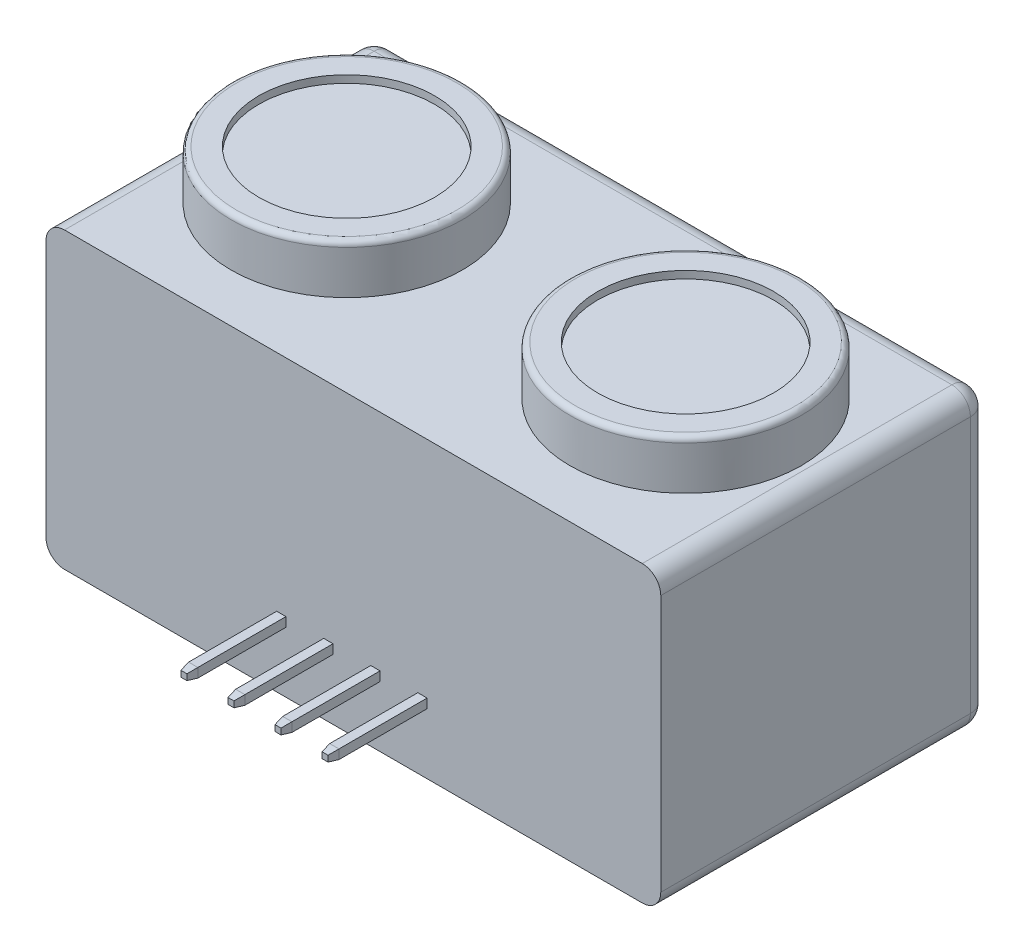
SolidWorks part; units mm, degrees
other "Camera1"
other "Camera3"
other "Camera4"
other "Camera5"
ref_plane "Front Plane" through (0, 0, 0) normal (0, 0, 1) x (1, 0, 0)
ref_plane "Top Plane" through (0, 0, 0) normal (0, 1, 0) x (1, 0, 0)
ref_plane "Right Plane" through (0, 0, 0) normal (1, 0, 0) x (0, 0, -1)
sketch "Sketch2" plane through (0, 0, 0) normal (0, 1, 0) x (1, 0, 0)
  line L1 (15.5, -8.5) -> (-15.5, -8.5)
  line L2 (15.5, -8.5) -> (15.5, 8.5)
  line L3 (15.5, 8.5) -> (-15.5, 8.5)
  line L4 (-15.5, -8.5) -> (-15.5, 8.5)
  line L5 (15.5, -8.5) -> (-15.5, 8.5) construction
  line L6 (15.5, 8.5) -> (-15.5, -8.5) construction
  point P0 (0, 0)
  dimension "D1" = 17
  dimension "D2" = 31
extrude "Boss-Extrude1" add sketch "Sketch2" along normal blind 1.5
sketch "Sketch3" plane through (0, 1.5, 0) normal (0, 1, 0) x (1, 0, 0)
  line L0 (0, 8.5) -> (0, -8.5) construction
  line L1 (15.5, 8.5) -> (-15.5, 8.5) construction
  line L2 (-15.5, -8.5) -> (15.5, -8.5) construction
  line L3 (-15.5, 8.5) -> (-15.5, -8.5) construction
  circle A0 centre (-9.15, 0) radius 6.25
  circle A1 centre (9.15, 0) radius 6.25
  point P10 (-15.4, 0)
  dimension "D1" = 12.5
  dimension "D2" = 0.1
extrude "Boss-Extrude2" add sketch "Sketch3" along normal blind 9
sketch "Sketch5" plane through (0, 0, 0) normal (0, -1, 0) x (1, 0, 0)
  line L0 (-15.5, 8.5) -> (15.5, 8.5) construction
  line L1 (-5.08, 5.86) -> (5.08, 5.86)
  line L2 (-5.08, 5.86) -> (-5.08, 8.4)
  line L3 (-5.08, 8.4) -> (5.08, 8.4)
  line L4 (5.08, 5.86) -> (5.08, 8.4)
  line L5 (-5.08, 7.13) -> (5.08, 7.13) construction
  line L6 (-2.54, 8.4) -> (-2.54, 5.86) construction
  line L7 (-3.56, 6.88) -> (-4.06, 6.88) construction
  line L8 (-3.56, 6.88) -> (-3.56, 7.38) construction
  line L9 (-3.56, 7.38) -> (-4.06, 7.38) construction
  line L10 (-4.06, 6.88) -> (-4.06, 7.38) construction
  line L11 (-3.56, 6.88) -> (-4.06, 7.38) construction
  line L12 (-3.56, 7.38) -> (-4.06, 6.88) construction
  line L13 (-4.06, 7.38) -> (-5.08, 7.38) construction
  line L14 (-4.06, 7.38) -> (-4.06, 8.4) construction
  line L15 (-3.56, 7.38) -> (-2.54, 7.38) construction
  line L16 (-1.52, 7.38) -> (-1.02, 7.38) construction
  line L17 (-1.02, 6.88) -> (-1.02, 7.38) construction
  line L18 (-1.52, 6.88) -> (-1.02, 6.88) construction
  line L19 (-1.52, 6.88) -> (-1.52, 7.38) construction
  line L20 (0, 7.13) -> (0, 8.4) construction
  line L21 (1.52, 6.88) -> (1.52, 7.38) construction
  line L22 (1.52, 6.88) -> (1.02, 6.88) construction
  line L23 (1.02, 6.88) -> (1.02, 7.38) construction
  line L24 (1.52, 7.38) -> (1.02, 7.38) construction
  line L25 (3.56, 7.38) -> (4.06, 7.38) construction
  line L26 (4.06, 6.88) -> (4.06, 7.38) construction
  line L27 (3.56, 6.88) -> (4.06, 6.88) construction
  line L28 (3.56, 6.88) -> (3.56, 7.38) construction
  line L29 (4.06, 7.38) -> (5.08, 7.38) construction
  line L30 (-1.02, 7.38) -> (0, 7.38) construction
  line L31 (-4.58, 8.4) -> (-5.08, 7.9)
  line L32 (-4.58, 5.86) -> (-5.08, 6.36)
  line L33 (-3.81, 7.13) -> (-3.81, 8.4) construction
  line L34 (-3.04, 5.86) -> (-2.54, 6.36)
  line L35 (-3.04, 8.4) -> (-2.54, 7.9)
  line L36 (-0.5, 8.4) -> (0, 7.9)
  line L37 (-0.5, 5.86) -> (0, 6.36)
  line L38 (-2.04, 5.86) -> (-2.54, 6.36)
  line L39 (-2.04, 8.4) -> (-2.54, 7.9)
  line L40 (4.58, 8.4) -> (5.08, 7.9)
  line L41 (4.58, 5.86) -> (5.08, 6.36)
  line L42 (3.04, 5.86) -> (2.54, 6.36)
  line L43 (3.04, 8.4) -> (2.54, 7.9)
  line L44 (2.04, 8.4) -> (2.54, 7.9)
  line L45 (2.04, 5.86) -> (2.54, 6.36)
  line L46 (0.5, 5.86) -> (0, 6.36)
  line L47 (0.5, 8.4) -> (0, 7.9)
  point P4 (0, 5.86)
  point P10 (-3.81, 7.13)
  dimension "D1" = 0.1
  dimension "D2" = 0.5
  dimension "D3" = 2.54
  dimension "D4" = 0.5
  dimension "D5" = 0.5
extrude "Boss-Extrude3" add sketch "Sketch5" along normal blind 2.5 contours L3 L47 L36 L39 L35 L31 L2 L32 L1 L34 L38 L37 L46 L45 L42 L41 L4 L40 L43 L44 region at (0, 0, 7.13)
sketch "Sketch6" plane through (0, -2.5, 0) normal (0, -1, 0) x (1, 0, 0)
  line L0 (-3.56, 6.88) -> (-4.06, 6.88) construction
  line L1 (-4.06, 6.88) -> (-4.06, 7.38) construction
  line L2 (-3.56, 7.38) -> (-4.06, 7.38) construction
  line L3 (-3.56, 6.88) -> (-3.56, 7.38) construction
  line L4 (-3.56, 6.88) -> (-4.06, 6.88)
  line L5 (-4.06, 6.88) -> (-4.06, 7.38)
  line L6 (-3.56, 7.38) -> (-4.06, 7.38)
  line L7 (-3.56, 6.88) -> (-3.56, 7.38)
  line L8 (-3.81, 6.88) -> (-3.81, 7.38) construction
ref_plane "Plane1" through (-3.81, 0, 0) normal (1, 0, 0) x (0, 0, -1)
sketch "Sketch7" plane through (-3.81, 0, 0) normal (1, 0, 0) x (0, 0, -1)
  line L0 (-7.13, -2.5) -> (-7.13, -3.5)
  line L1 (-6.88, -2.5) -> (-7.38, -2.5) construction
  line L2 (-8.13, -4.5) -> (-14.13, -4.5)
  arc A0 (-7.13, -3.5) -> (-8.13, -4.5) centre (-8.13, -3.5) cw
  point P7 (-7.13, -4.5)
  dimension "D3" = 1
  dimension "D1" = 2
  dimension "D2" = 7
sweep "Sweep1" add profiles "Sketch6" path "Sketch7"
pattern_linear "LPattern1" count 4 spacing 2.54 along (1, 0, 0) of "Sweep1"
chamfer "Chamfer1" distance 0.5 angle 10 16 edges at (-3.81, -4.75, 14.13) (-4.06, -4.5, 14.13) (-3.81, -4.25, 14.13) (-3.56, -4.5, 14.13) (-1.27, -4.75, 14.13) (-1.52, -4.5, 14.13) (-1.27, -4.25, 14.13) (-1.02, -4.5, 14.13) (1.27, -4.75, 14.13) (1.02, -4.5, 14.13) (1.27, -4.25, 14.13) (1.52, -4.5, 14.13) (3.81, -4.75, 14.13) (3.56, -4.5, 14.13) (3.81, -4.25, 14.13) (4.06, -4.5, 14.13) first distance on face at (-3.81, -4.75, 11.13) first distance on face at (-4.06, -4.5, 11.13) first distance on face at (-3.81, -4.25, 11.13) first distance on face at (-3.56, -4.5, 11.13) first distance on face at (-1.27, -4.75, 11.13) first distance on face at (-1.52, -4.5, 11.13) first distance on face at (-1.27, -4.25, 11.13) first distance on face at (-1.02, -4.5, 11.13) first distance on face at (1.27, -4.75, 11.13) first distance on face at (1.02, -4.5, 11.13) first distance on face at (1.27, -4.25, 11.13) first distance on face at (1.52, -4.5, 11.13) first distance on face at (3.81, -4.75, 11.13) first distance on face at (3.56, -4.5, 11.13) first distance on face at (3.81, -4.25, 11.13) first distance on face at (4.06, -4.5, 11.13)
sketch "Sketch8" plane through (0, 0, 0) normal (0, 0, 1) x (1, 0, 0)
  line L0 (-9.15, 10.5) -> (-9.15, 1.5)
  line L1 (-2.9, 10.5) -> (-15.4, 10.5) construction
  line L2 (-15.5, 1.5) -> (15.5, 1.5) construction
  line L3 (9.15, 10.5) -> (9.15, 1.5)
  line L4 (15.4, 10.5) -> (2.9, 10.5) construction
  line L6 (-15.4, 10.5) -> (-15.4, 1.5) construction
  line L7 (-15.4, 2.5) -> (-15.5586, 2.5)
  line L8 (-15.5586, 2.5) -> (-15.5586, 1.5)
  line L9 (-15.5586, 1.5) -> (-14.4, 1.5)
  line L10 (0, 0) -> (0, 10.5) construction
  line L11 (15.5586, 1.5) -> (14.4, 1.5)
  line L12 (15.5586, 2.5) -> (15.5586, 1.5)
  line L13 (15.4, 2.5) -> (15.5586, 2.5)
  circle A0 centre (-14.4, 2.5) radius 1
  circle A1 centre (14.4, 2.5) radius 1
  dimension "D1" = 2
revolve "Cut-Revolve1" cut sketch "Sketch8" angle 360 about L0 region at (-15.3053, 1.8409, 0)
revolve "Cut-Revolve2" cut sketch "Sketch8<4>" angle 360 about L3 region at (15.3053, 1.8409, 0)
sketch "Sketch8<4>" plane through (0, 0, 0) normal (0, 0, 1) x (1, 0, 0) same geometry as "Sketch8"
sketch "Sketch9" plane through (0, 10.5, 0) normal (0, 1, 0) x (1, 0, 0)
  line L0 (0, 0) -> (0, 8.5) construction
  line L1 (15.5, 8.5) -> (-15.5, 8.5) construction
  circle A1 centre (9.15, 0) radius 4.75
  circle A2 centre (-9.15, 0) radius 4.75
  circle A3 centre (-9.15, 0) radius 4.75
  dimension "D1" = 1.5
extrude "Cut-Extrude1" cut sketch "Sketch9" against normal blind 3
sketch "Sketch10" plane through (0, 7.5, 0) normal (0, 1, 0) x (1, 0, 0)
  line L0 (0, 0) -> (0, 8.5) construction
  line L1 (15.5, 8.5) -> (-15.5, 8.5) construction
  circle A1 centre (9.15, 0) radius 3.25
  circle A2 centre (-9.15, 0) radius 3.25
  circle A3 centre (-9.15, 0) radius 3.25
  dimension "D1" = 1.5
extrude "Boss-Extrude4" add sketch "Sketch10" along normal blind 0.2
fillet "Fillet1" radius 0.3 2 edges at (9.15, 10.5, -6.25) (-9.15, 10.5, 6.25)
sketch "Sketch11" plane through (0, 1.5, 0) normal (0, 1, 0) x (1, 0, 0)
  line L0 (3.56, -6.88) -> (3.56, -7.38) construction
  line L1 (3.56, -7.38) -> (4.06, -7.38) construction
  line L2 (4.06, -6.88) -> (4.06, -7.38) construction
  line L3 (3.56, -6.88) -> (4.06, -6.88) construction
  line L4 (1.02, -6.88) -> (1.02, -7.38) construction
  line L5 (1.52, -6.88) -> (1.52, -7.38) construction
  line L6 (1.52, -6.88) -> (1.02, -6.88) construction
  line L7 (1.52, -7.38) -> (1.02, -7.38) construction
  line L8 (-1.52, -7.38) -> (-1.02, -7.38) construction
  line L9 (-1.52, -6.88) -> (-1.52, -7.38) construction
  line L10 (-1.52, -6.88) -> (-1.02, -6.88) construction
  line L11 (-3.56, -7.38) -> (-4.06, -7.38) construction
  line L12 (-3.56, -6.88) -> (-3.56, -7.38) construction
  line L13 (-3.56, -6.88) -> (-4.06, -6.88) construction
  line L14 (-4.06, -6.88) -> (-4.06, -7.38) construction
  line L15 (3.56, -6.88) -> (3.56, -7.38)
  line L16 (3.56, -7.38) -> (4.06, -7.38)
  line L17 (4.06, -6.88) -> (4.06, -7.38)
  line L18 (3.56, -6.88) -> (4.06, -6.88)
  line L19 (1.02, -6.88) -> (1.02, -7.38)
  line L20 (1.52, -6.88) -> (1.52, -7.38)
  line L21 (1.52, -6.88) -> (1.02, -6.88)
  line L22 (1.52, -7.38) -> (1.02, -7.38)
  line L23 (-1.52, -7.38) -> (-1.02, -7.38)
  line L24 (-1.52, -6.88) -> (-1.52, -7.38)
  line L25 (-1.52, -6.88) -> (-1.02, -6.88)
  line L26 (-3.56, -7.38) -> (-4.06, -7.38)
  line L27 (-3.56, -6.88) -> (-3.56, -7.38)
  line L28 (-3.56, -6.88) -> (-4.06, -6.88)
  line L29 (-4.06, -6.88) -> (-4.06, -7.38)
  line L30 (-1.02, -6.88) -> (-1.02, -7.38) construction
  line L31 (-1.02, -6.88) -> (-1.02, -7.38)
extrude "Boss-Extrude5" add sketch "Sketch11" along normal blind 1.5
sketch "Sketch12" plane through (0, 1.5, 0) normal (0, 1, 0) x (1, 0, 0)
  line L0 (0, 0) -> (0, 8.5) construction
  line L1 (15.5, 8.5) -> (-15.5, 8.5) construction
  line L2 (0, 0) -> (-15.5, 0) construction
  line L3 (-15.5, 8.5) -> (-15.5, -8.5) construction
  circle A0 centre (-13.85, 6.85) radius 1.15
  circle A1 centre (-13.85, -6.85) radius 1.15
  circle A2 centre (13.85, 6.85) radius 1.15
  circle A3 centre (13.85, -6.85) radius 1.15
  point P7 (-13.85, 8)
  point P11 (-15, 6.85)
  dimension "D1" = 2.3
  dimension "D2" = 0.5
  dimension "D3" = 0.5
extrude "Cut-Extrude2" cut sketch "Sketch12" against normal through all
sketch "Sketch13" plane through (0, 0, 0) normal (0, -1, 0) x (1, 0, 0)
  line L0 (-1.8777, -0.2081) -> (-5.5777, -0.2081)
  line L1 (6.0559, -5.453) -> (2.3559, -5.453)
  line L2 (6.0559, -5.453) -> (6.0559, 3.047)
  line L3 (6.0559, 3.047) -> (2.3559, 3.047)
  line L4 (2.3559, -5.453) -> (2.3559, 3.047)
  line L5 (-1.8777, -5.8501) -> (-5.5777, -5.8501)
  line L6 (-1.8777, -5.8501) -> (-1.8777, -1.0501)
  line L7 (-1.8777, -1.0501) -> (-5.5777, -1.0501)
  line L8 (-5.5777, -5.8501) -> (-5.5777, -1.0501)
  line L9 (-1.8777, -0.2081) -> (-1.8777, 4.5919)
  line L10 (-1.8777, 4.5919) -> (-5.5777, 4.5919)
  line L11 (-5.5777, -0.2081) -> (-5.5777, 4.5919)
  dimension "D1" = 8.5
  dimension "D2" = 3.7
  dimension "D3" = 4.8
extrude "Boss-Extrude6" add sketch "Sketch13" along normal blind 1.8
sketch "Sketch15" plane through (0, 0, 0) normal (0, -1, 0) x (1, 0, 0)
  line L0 (-7.4016, 7.4233) -> (-6.6016, 7.4233)
  line L1 (6.5088, 7.4233) -> (7.3088, 7.4233) construction
  line L2 (6.5088, 7.4233) -> (6.5088, 5.7233) construction
  line L3 (6.5088, 5.7233) -> (7.3088, 5.7233) construction
  line L4 (7.3088, 7.4233) -> (7.3088, 5.7233) construction
  line L5 (-7.4016, 7.4233) -> (-7.4016, 5.7233)
  line L6 (-7.4016, 5.7233) -> (-6.6016, 5.7233)
  line L7 (-6.6016, 7.4233) -> (-6.6016, 5.7233)
  line L8 (11.4023, 0.8225) -> (12.2023, 0.8225)
  line L9 (11.4023, 0.8225) -> (11.4023, -0.8775)
  line L10 (11.4023, -0.8775) -> (12.2023, -0.8775)
  line L11 (12.2023, 0.8225) -> (12.2023, -0.8775)
  line L12 (12.9586, 0.8225) -> (13.7586, 0.8225)
  line L13 (12.9586, 0.8225) -> (12.9586, -0.8775)
  line L14 (12.9586, -0.8775) -> (13.7586, -0.8775)
  line L15 (13.7586, 0.8225) -> (13.7586, -0.8775)
  line L16 (-13.5973, 3.4847) -> (-13.5973, 4.2847) construction
  line L17 (-13.5973, 3.4847) -> (-11.8973, 3.4847) construction
  line L18 (-11.8973, 3.4847) -> (-11.8973, 4.2847) construction
  line L19 (-13.5973, 4.2847) -> (-11.8973, 4.2847) construction
  line L24 (-10.4102, -0.5325) -> (-10.4102, 0.2675) construction
  line L25 (-10.4102, -0.5325) -> (-8.7102, -0.5325) construction
  line L26 (-8.7102, -0.5325) -> (-8.7102, 0.2675) construction
  line L27 (-10.4102, 0.2675) -> (-8.7102, 0.2675) construction
  line L28 (8.4741, -0.5474) -> (8.4741, 0.2526) construction
  line L29 (8.4741, -0.5474) -> (10.1741, -0.5474) construction
  line L30 (10.1741, -0.5474) -> (10.1741, 0.2526) construction
  line L31 (8.4741, 0.2526) -> (10.1741, 0.2526) construction
  line L32 (11.7611, 3.4552) -> (11.7611, 4.2552) construction
  line L33 (11.7611, 3.4552) -> (13.4611, 3.4552) construction
  line L34 (13.4611, 3.4552) -> (13.4611, 4.2552) construction
  line L35 (11.7611, 4.2552) -> (13.4611, 4.2552) construction
  line L36 (11.7611, 1.9552) -> (11.7611, 2.7552)
  line L37 (11.7611, 1.9552) -> (13.4611, 1.9552)
  line L38 (13.4611, 1.9552) -> (13.4611, 2.7552)
  line L39 (11.7611, 2.7552) -> (13.4611, 2.7552)
  line L40 (11.7611, -2.7466) -> (11.7611, -1.9466) construction
  line L41 (11.7611, -2.7466) -> (13.4611, -2.7466) construction
  line L42 (13.4611, -2.7466) -> (13.4611, -1.9466) construction
  line L43 (11.7611, -1.9466) -> (13.4611, -1.9466) construction
  line L44 (11.7611, -4.2466) -> (11.7611, -3.4466) construction
  line L45 (11.7611, -3.4466) -> (13.4611, -3.4466) construction
  line L46 (13.4611, -4.2466) -> (13.4611, -3.4466) construction
  line L47 (11.7611, -4.2466) -> (13.4611, -4.2466) construction
  line L48 (-13.5973, 1.9347) -> (-13.5973, 2.7347) construction
  line L49 (-13.5973, 2.7347) -> (-11.8973, 2.7347) construction
  line L50 (-11.8973, 1.9347) -> (-11.8973, 2.7347) construction
  line L51 (-13.5973, 1.9347) -> (-11.8973, 1.9347) construction
  line L52 (-13.5973, 0.3847) -> (-13.5973, 1.1847)
  line L53 (-13.5973, 1.1847) -> (-11.8973, 1.1847)
  line L54 (-11.8973, 0.3847) -> (-11.8973, 1.1847)
  line L55 (-13.5973, 0.3847) -> (-11.8973, 0.3847)
  line L56 (-13.5973, -1.1653) -> (-13.5973, -0.3653) construction
  line L57 (-13.5973, -0.3653) -> (-11.8973, -0.3653) construction
  line L58 (-11.8973, -1.1653) -> (-11.8973, -0.3653) construction
  line L59 (-13.5973, -1.1653) -> (-11.8973, -1.1653) construction
  line L60 (-13.5973, -2.7153) -> (-13.5973, -1.9153) construction
  line L61 (-13.5973, -1.9153) -> (-11.8973, -1.9153) construction
  line L62 (-11.8973, -2.7153) -> (-11.8973, -1.9153) construction
  line L63 (-13.5973, -2.7153) -> (-11.8973, -2.7153) construction
  line L64 (-13.5973, -4.2653) -> (-13.5973, -3.4653)
  line L65 (-13.5973, -3.4653) -> (-11.8973, -3.4653)
  line L66 (-11.8973, -4.2653) -> (-11.8973, -3.4653)
  line L67 (-13.5973, -4.2653) -> (-11.8973, -4.2653)
  line L68 (-9.8363, -7.297) -> (-9.8363, -6.497) construction
  line L69 (-9.8363, -7.297) -> (-8.1363, -7.297) construction
  line L70 (-8.1363, -7.297) -> (-8.1363, -6.497) construction
  line L71 (-9.8363, -6.497) -> (-8.1363, -6.497) construction
  line L72 (-6.8363, -7.297) -> (-6.8363, -6.497)
  line L73 (-6.8363, -7.297) -> (-5.1363, -7.297)
  line L74 (-5.1363, -7.297) -> (-5.1363, -6.497)
  line L75 (-6.8363, -6.497) -> (-5.1363, -6.497)
  line L76 (-3.8363, -7.297) -> (-3.8363, -6.497) construction
  line L77 (-3.8363, -7.297) -> (-2.1363, -7.297) construction
  line L78 (-2.1363, -7.297) -> (-2.1363, -6.497) construction
  line L79 (-3.8363, -6.497) -> (-2.1363, -6.497) construction
  line L80 (-0.8363, -7.297) -> (-0.8363, -6.497) construction
  line L81 (-0.8363, -7.297) -> (0.8637, -7.297) construction
  line L82 (0.8637, -7.297) -> (0.8637, -6.497) construction
  line L83 (-0.8363, -6.497) -> (0.8637, -6.497) construction
  line L84 (2.7977, -7.297) -> (2.7977, -6.497) construction
  line L85 (2.7977, -7.297) -> (4.4977, -7.297) construction
  line L86 (4.4977, -7.297) -> (4.4977, -6.497) construction
  line L87 (2.7977, -6.497) -> (4.4977, -6.497) construction
  line L88 (5.7977, -7.297) -> (5.7977, -6.497) construction
  line L89 (5.7977, -6.497) -> (7.4977, -6.497) construction
  line L90 (7.4977, -7.297) -> (7.4977, -6.497) construction
  line L91 (5.7977, -7.297) -> (7.4977, -7.297) construction
  line L92 (8.7977, -7.297) -> (8.7977, -6.497)
  line L93 (8.7977, -6.497) -> (10.4977, -6.497)
  line L94 (10.4977, -7.297) -> (10.4977, -6.497)
  line L95 (8.7977, -7.297) -> (10.4977, -7.297)
  line L96 (2.3858, 3.9722) -> (2.3858, 4.7722) construction
  line L97 (2.3858, 3.9722) -> (4.0858, 3.9722) construction
  line L98 (4.0858, 3.9722) -> (4.0858, 4.7722) construction
  line L99 (2.3858, 4.7722) -> (4.0858, 4.7722) construction
  line L100 (5.3589, 3.9722) -> (5.3589, 4.7722) construction
  line L101 (5.3589, 3.9722) -> (7.0589, 3.9722) construction
  line L102 (7.0589, 3.9722) -> (7.0589, 4.7722) construction
  line L103 (5.3589, 4.7722) -> (7.0589, 4.7722) construction
  dimension "D1" = 1.7
  dimension "D2" = 0.8
  dimension "D3" = 2
  dimension "D4" = 2
  dimension "D5" = 6
  dimension "D6" = 4
  dimension "D7" = 3
extrude "Boss-Extrude7" add sketch "Sketch15" along normal blind 1
sketch "Sketch16" plane through (0, 0, 0) normal (0, -1, 0) x (1, 0, 0)
  line L0 (-13.5973, 1.9347) -> (-11.8973, 1.9347) construction
  line L1 (-13.5973, 1.9347) -> (-13.5973, 2.7347) construction
  line L2 (-13.5973, 2.7347) -> (-11.8973, 2.7347) construction
  line L3 (-11.8973, 1.9347) -> (-11.8973, 2.7347) construction
  line L12 (-11.8973, 3.4847) -> (-11.8973, 4.2847) construction
  line L13 (-13.5973, 3.4847) -> (-11.8973, 3.4847) construction
  line L14 (-13.5973, 3.4847) -> (-13.5973, 4.2847) construction
  line L15 (-13.5973, 4.2847) -> (-11.8973, 4.2847) construction
  line L16 (-8.7102, -0.5325) -> (-8.7102, 0.2675) construction
  line L17 (-10.4102, 0.2675) -> (-8.7102, 0.2675) construction
  line L18 (-10.4102, -0.5325) -> (-8.7102, -0.5325) construction
  line L19 (-10.4102, -0.5325) -> (-10.4102, 0.2675) construction
  line L20 (-11.8973, -1.1653) -> (-11.8973, -0.3653) construction
  line L21 (-13.5973, -0.3653) -> (-11.8973, -0.3653) construction
  line L22 (-13.5973, -1.1653) -> (-13.5973, -0.3653) construction
  line L23 (-13.5973, -1.1653) -> (-11.8973, -1.1653) construction
  line L24 (-13.5973, -2.7153) -> (-13.5973, -1.9153) construction
  line L25 (-13.5973, -1.9153) -> (-11.8973, -1.9153) construction
  line L26 (-11.8973, -2.7153) -> (-11.8973, -1.9153) construction
  line L27 (-13.5973, -2.7153) -> (-11.8973, -2.7153) construction
  line L28 (-8.1363, -7.297) -> (-8.1363, -6.497) construction
  line L29 (-9.8363, -6.497) -> (-8.1363, -6.497) construction
  line L30 (-9.8363, -7.297) -> (-9.8363, -6.497) construction
  line L31 (-9.8363, -7.297) -> (-8.1363, -7.297) construction
  line L32 (0.8637, -7.297) -> (0.8637, -6.497) construction
  line L33 (-0.8363, -7.297) -> (0.8637, -7.297) construction
  line L34 (-0.8363, -7.297) -> (-0.8363, -6.497) construction
  line L35 (-0.8363, -6.497) -> (0.8637, -6.497) construction
  line L36 (-2.1363, -7.297) -> (-2.1363, -6.497) construction
  line L37 (-3.8363, -6.497) -> (-2.1363, -6.497) construction
  line L38 (-3.8363, -7.297) -> (-3.8363, -6.497) construction
  line L39 (-3.8363, -7.297) -> (-2.1363, -7.297) construction
  line L40 (2.7977, -7.297) -> (2.7977, -6.497) construction
  line L41 (2.7977, -6.497) -> (4.4977, -6.497) construction
  line L42 (2.7977, -7.297) -> (4.4977, -7.297) construction
  line L43 (4.4977, -7.297) -> (4.4977, -6.497) construction
  line L44 (7.4977, -7.297) -> (7.4977, -6.497) construction
  line L45 (5.7977, -6.497) -> (7.4977, -6.497) construction
  line L46 (5.7977, -7.297) -> (5.7977, -6.497) construction
  line L47 (5.7977, -7.297) -> (7.4977, -7.297) construction
  line L48 (13.4611, -2.7466) -> (13.4611, -1.9466) construction
  line L49 (11.7611, -1.9466) -> (13.4611, -1.9466) construction
  line L50 (11.7611, -2.7466) -> (11.7611, -1.9466) construction
  line L51 (11.7611, -2.7466) -> (13.4611, -2.7466) construction
  line L52 (13.4611, -4.2466) -> (13.4611, -3.4466) construction
  line L53 (11.7611, -3.4466) -> (13.4611, -3.4466) construction
  line L54 (11.7611, -4.2466) -> (11.7611, -3.4466) construction
  line L55 (11.7611, -4.2466) -> (13.4611, -4.2466) construction
  line L56 (10.1741, -0.5474) -> (10.1741, 0.2526) construction
  line L57 (8.4741, -0.5474) -> (10.1741, -0.5474) construction
  line L58 (8.4741, -0.5474) -> (8.4741, 0.2526) construction
  line L59 (8.4741, 0.2526) -> (10.1741, 0.2526) construction
  line L60 (11.7611, 3.4552) -> (13.4611, 3.4552) construction
  line L61 (11.7611, 3.4552) -> (11.7611, 4.2552) construction
  line L62 (11.7611, 4.2552) -> (13.4611, 4.2552) construction
  line L63 (13.4611, 3.4552) -> (13.4611, 4.2552) construction
  line L64 (6.5088, 7.4233) -> (7.3088, 7.4233) construction
  line L65 (6.5088, 7.4233) -> (6.5088, 5.7233) construction
  line L66 (7.3088, 7.4233) -> (7.3088, 5.7233) construction
  line L67 (6.5088, 5.7233) -> (7.3088, 5.7233) construction
  line L68 (7.0589, 3.9722) -> (7.0589, 4.7722) construction
  line L69 (5.3589, 3.9722) -> (7.0589, 3.9722) construction
  line L70 (5.3589, 4.7722) -> (7.0589, 4.7722) construction
  line L71 (5.3589, 3.9722) -> (5.3589, 4.7722) construction
  line L72 (2.3858, 3.9722) -> (2.3858, 4.7722) construction
  line L73 (2.3858, 3.9722) -> (4.0858, 3.9722) construction
  line L74 (4.0858, 3.9722) -> (4.0858, 4.7722) construction
  line L75 (2.3858, 4.7722) -> (4.0858, 4.7722) construction
  line L76 (-13.5973, 1.9347) -> (-11.8973, 1.9347)
  line L77 (-13.5973, 1.9347) -> (-13.5973, 2.7347)
  line L78 (-13.5973, 2.7347) -> (-11.8973, 2.7347)
  line L79 (-11.8973, 1.9347) -> (-11.8973, 2.7347)
  line L80 (-11.8973, 3.4847) -> (-11.8973, 4.2847)
  line L81 (-13.5973, 3.4847) -> (-11.8973, 3.4847)
  line L82 (-13.5973, 3.4847) -> (-13.5973, 4.2847)
  line L83 (-13.5973, 4.2847) -> (-11.8973, 4.2847)
  line L84 (-8.7102, -0.5325) -> (-8.7102, 0.2675)
  line L85 (-10.4102, 0.2675) -> (-8.7102, 0.2675)
  line L86 (-10.4102, -0.5325) -> (-8.7102, -0.5325)
  line L87 (-10.4102, -0.5325) -> (-10.4102, 0.2675)
  line L88 (-11.8973, -1.1653) -> (-11.8973, -0.3653)
  line L89 (-13.5973, -0.3653) -> (-11.8973, -0.3653)
  line L90 (-13.5973, -1.1653) -> (-13.5973, -0.3653)
  line L91 (-13.5973, -1.1653) -> (-11.8973, -1.1653)
  line L92 (-13.5973, -2.7153) -> (-13.5973, -1.9153)
  line L93 (-13.5973, -1.9153) -> (-11.8973, -1.9153)
  line L94 (-11.8973, -2.7153) -> (-11.8973, -1.9153)
  line L95 (-13.5973, -2.7153) -> (-11.8973, -2.7153)
  line L96 (-8.1363, -7.297) -> (-8.1363, -6.497)
  line L97 (-9.8363, -6.497) -> (-8.1363, -6.497)
  line L98 (-9.8363, -7.297) -> (-9.8363, -6.497)
  line L99 (-9.8363, -7.297) -> (-8.1363, -7.297)
  line L100 (0.8637, -7.297) -> (0.8637, -6.497)
  line L101 (-0.8363, -7.297) -> (0.8637, -7.297)
  line L102 (-0.8363, -7.297) -> (-0.8363, -6.497)
  line L103 (-0.8363, -6.497) -> (0.8637, -6.497)
  line L104 (-2.1363, -7.297) -> (-2.1363, -6.497)
  line L105 (-3.8363, -6.497) -> (-2.1363, -6.497)
  line L106 (-3.8363, -7.297) -> (-3.8363, -6.497)
  line L107 (-3.8363, -7.297) -> (-2.1363, -7.297)
  line L108 (2.7977, -7.297) -> (2.7977, -6.497)
  line L109 (2.7977, -6.497) -> (4.4977, -6.497)
  line L110 (2.7977, -7.297) -> (4.4977, -7.297)
  line L111 (4.4977, -7.297) -> (4.4977, -6.497)
  line L112 (7.4977, -7.297) -> (7.4977, -6.497)
  line L113 (5.7977, -6.497) -> (7.4977, -6.497)
  line L114 (5.7977, -7.297) -> (5.7977, -6.497)
  line L115 (5.7977, -7.297) -> (7.4977, -7.297)
  line L116 (13.4611, -2.7466) -> (13.4611, -1.9466)
  line L117 (11.7611, -1.9466) -> (13.4611, -1.9466)
  line L118 (11.7611, -2.7466) -> (11.7611, -1.9466)
  line L119 (11.7611, -2.7466) -> (13.4611, -2.7466)
  line L120 (13.4611, -4.2466) -> (13.4611, -3.4466)
  line L121 (11.7611, -3.4466) -> (13.4611, -3.4466)
  line L122 (11.7611, -4.2466) -> (11.7611, -3.4466)
  line L123 (11.7611, -4.2466) -> (13.4611, -4.2466)
  line L124 (10.1741, -0.5474) -> (10.1741, 0.2526)
  line L125 (8.4741, -0.5474) -> (10.1741, -0.5474)
  line L126 (8.4741, -0.5474) -> (8.4741, 0.2526)
  line L127 (8.4741, 0.2526) -> (10.1741, 0.2526)
  line L128 (11.7611, 3.4552) -> (13.4611, 3.4552)
  line L129 (11.7611, 3.4552) -> (11.7611, 4.2552)
  line L130 (11.7611, 4.2552) -> (13.4611, 4.2552)
  line L131 (13.4611, 3.4552) -> (13.4611, 4.2552)
  line L132 (6.5088, 7.4233) -> (7.3088, 7.4233)
  line L133 (6.5088, 7.4233) -> (6.5088, 5.7233)
  line L134 (7.3088, 7.4233) -> (7.3088, 5.7233)
  line L135 (6.5088, 5.7233) -> (7.3088, 5.7233)
  line L136 (7.0589, 3.9722) -> (7.0589, 4.7722)
  line L137 (5.3589, 3.9722) -> (7.0589, 3.9722)
  line L138 (5.3589, 4.7722) -> (7.0589, 4.7722)
  line L139 (5.3589, 3.9722) -> (5.3589, 4.7722)
  line L140 (2.3858, 3.9722) -> (2.3858, 4.7722)
  line L141 (2.3858, 3.9722) -> (4.0858, 3.9722)
  line L142 (4.0858, 3.9722) -> (4.0858, 4.7722)
  line L143 (2.3858, 4.7722) -> (4.0858, 4.7722)
extrude "Boss-Extrude8" add sketch "Sketch16" along normal blind 0.5
sketch "Sketch17" plane through (0, 0, 0) normal (0, -1, 0) x (1, 0, 0)
  line L0 (-1.8777, -0.2081) -> (-1.8777, 4.5919) construction
  line L1 (-2.7294, 4.1419) -> (-0.3777, 4.1419)
  line L2 (-2.7294, 4.1419) -> (-2.7294, 3.8419)
  line L3 (-2.7294, 3.8419) -> (-0.3777, 3.8419)
  line L4 (-0.3777, 4.1419) -> (-0.3777, 3.8419)
  line L5 (-3.7277, 4.5919) -> (-3.7277, -0.2081) construction
  line L6 (-1.8777, 4.5919) -> (-5.5777, 4.5919) construction
  line L7 (-5.5777, -0.2081) -> (-1.8777, -0.2081) construction
  line L32 (-2.7294, 4.1419) -> (-2.7294, 4.5919) construction
  line L33 (-1.8777, 4.5919) -> (-5.5777, 4.5919) construction
  line L66 (-2.7294, 2.9419) -> (-2.7294, 2.6419)
  line L67 (-2.7294, 2.9419) -> (-0.3777, 2.9419)
  line L68 (-0.3777, 2.9419) -> (-0.3777, 2.6419)
  line L69 (-2.7294, 2.6419) -> (-0.3777, 2.6419)
  line L70 (-2.7294, 1.7419) -> (-2.7294, 1.4419)
  line L71 (-2.7294, 1.7419) -> (-0.3777, 1.7419)
  line L72 (-0.3777, 1.7419) -> (-0.3777, 1.4419)
  line L73 (-2.7294, 1.4419) -> (-0.3777, 1.4419)
  line L74 (-2.7294, 0.5419) -> (-2.7294, 0.2419)
  line L75 (-2.7294, 0.5419) -> (-0.3777, 0.5419)
  line L76 (-0.3777, 0.5419) -> (-0.3777, 0.2419)
  line L77 (-2.7294, 0.2419) -> (-0.3777, 0.2419)
  line L78 (-2.7294, 0.2419) -> (-2.7294, -0.2081) construction
  line L79 (-4.7261, 0.5419) -> (-7.0777, 0.5419)
  line L80 (-7.0777, 0.5419) -> (-7.0777, 0.2419)
  line L81 (-4.7261, 0.2419) -> (-7.0777, 0.2419)
  line L82 (-4.7261, 0.5419) -> (-4.7261, 0.2419)
  line L83 (-4.7261, 1.7419) -> (-7.0777, 1.7419)
  line L84 (-7.0777, 1.7419) -> (-7.0777, 1.4419)
  line L85 (-4.7261, 1.4419) -> (-7.0777, 1.4419)
  line L86 (-4.7261, 1.7419) -> (-4.7261, 1.4419)
  line L87 (-4.7261, 2.9419) -> (-7.0777, 2.9419)
  line L88 (-7.0777, 2.9419) -> (-7.0777, 2.6419)
  line L89 (-4.7261, 2.6419) -> (-7.0777, 2.6419)
  line L90 (-4.7261, 2.9419) -> (-4.7261, 2.6419)
  line L91 (-4.7261, 3.8419) -> (-7.0777, 3.8419)
  line L92 (-7.0777, 4.1419) -> (-7.0777, 3.8419)
  line L93 (-4.7261, 4.1419) -> (-7.0777, 4.1419)
  line L94 (-4.7261, 4.1419) -> (-4.7261, 3.8419)
  line L95 (-5.5777, -0.2081) -> (-5.5777, -1.0501) construction
  line L96 (-5.5777, -0.6291) -> (2.3559, -0.6291) construction
  line L97 (2.3559, 3.047) -> (2.3559, -5.453) construction
  line L98 (-4.7261, -1.8001) -> (-4.7261, -1.5001)
  line L99 (-4.7261, -1.5001) -> (-7.0777, -1.5001)
  line L100 (-7.0777, -1.8001) -> (-7.0777, -1.5001)
  line L101 (-4.7261, -1.8001) -> (-7.0777, -1.8001)
  line L102 (-4.7261, -3.0001) -> (-4.7261, -2.7001)
  line L103 (-4.7261, -2.7001) -> (-7.0777, -2.7001)
  line L104 (-7.0777, -3.0001) -> (-7.0777, -2.7001)
  line L105 (-4.7261, -3.0001) -> (-7.0777, -3.0001)
  line L106 (-4.7261, -4.2001) -> (-4.7261, -3.9001)
  line L107 (-4.7261, -3.9001) -> (-7.0777, -3.9001)
  line L108 (-7.0777, -4.2001) -> (-7.0777, -3.9001)
  line L109 (-4.7261, -4.2001) -> (-7.0777, -4.2001)
  line L110 (-4.7261, -5.4001) -> (-4.7261, -5.1001)
  line L111 (-4.7261, -5.4001) -> (-7.0777, -5.4001)
  line L112 (-7.0777, -5.4001) -> (-7.0777, -5.1001)
  line L113 (-4.7261, -5.1001) -> (-7.0777, -5.1001)
  line L114 (-2.7294, -5.1001) -> (-0.3777, -5.1001)
  line L115 (-0.3777, -5.4001) -> (-0.3777, -5.1001)
  line L116 (-2.7294, -5.4001) -> (-0.3777, -5.4001)
  line L117 (-2.7294, -5.4001) -> (-2.7294, -5.1001)
  line L118 (-2.7294, -4.2001) -> (-0.3777, -4.2001)
  line L119 (-0.3777, -4.2001) -> (-0.3777, -3.9001)
  line L120 (-2.7294, -3.9001) -> (-0.3777, -3.9001)
  line L121 (-2.7294, -4.2001) -> (-2.7294, -3.9001)
  line L122 (-2.7294, -3.0001) -> (-0.3777, -3.0001)
  line L123 (-0.3777, -3.0001) -> (-0.3777, -2.7001)
  line L124 (-2.7294, -2.7001) -> (-0.3777, -2.7001)
  line L125 (-2.7294, -3.0001) -> (-2.7294, -2.7001)
  line L126 (-2.7294, -1.8001) -> (-0.3777, -1.8001)
  line L127 (-0.3777, -1.8001) -> (-0.3777, -1.5001)
  line L128 (-2.7294, -1.5001) -> (-0.3777, -1.5001)
  line L129 (-2.7294, -1.8001) -> (-2.7294, -1.5001)
  line L130 (5.2043, 2.551) -> (5.2043, 2.2431)
  line L131 (5.2043, 2.551) -> (7.5559, 2.551)
  line L132 (7.5559, 2.551) -> (7.5559, 2.2431)
  line L133 (5.2043, 2.2431) -> (7.5559, 2.2431)
  line L134 (6.0559, -5.453) -> (6.0559, 3.047) construction
  line L135 (5.2043, 2.551) -> (5.2043, 3.047) construction
  line L136 (6.0559, 3.047) -> (2.3559, 3.047) construction
  line L137 (5.2043, 1.351) -> (5.2043, 1.0431)
  line L138 (5.2043, 1.0431) -> (7.5559, 1.0431)
  line L139 (7.5559, 1.351) -> (7.5559, 1.0431)
  line L140 (5.2043, 1.351) -> (7.5559, 1.351)
  line L141 (5.2043, 0.151) -> (5.2043, -0.1569)
  line L142 (5.2043, -0.1569) -> (7.5559, -0.1569)
  line L143 (7.5559, 0.151) -> (7.5559, -0.1569)
  line L144 (5.2043, 0.151) -> (7.5559, 0.151)
  line L145 (5.2043, -1.049) -> (5.2043, -1.3569)
  line L146 (5.2043, -1.3569) -> (7.5559, -1.3569)
  line L147 (7.5559, -1.049) -> (7.5559, -1.3569)
  line L148 (5.2043, -1.049) -> (7.5559, -1.049)
  line L149 (5.2043, -2.249) -> (5.2043, -2.5569)
  line L150 (5.2043, -2.5569) -> (7.5559, -2.5569)
  line L151 (7.5559, -2.249) -> (7.5559, -2.5569)
  line L152 (5.2043, -2.249) -> (7.5559, -2.249)
  line L153 (5.2043, -3.449) -> (5.2043, -3.7569)
  line L154 (5.2043, -3.7569) -> (7.5559, -3.7569)
  line L155 (7.5559, -3.449) -> (7.5559, -3.7569)
  line L156 (5.2043, -3.449) -> (7.5559, -3.449)
  line L157 (5.2043, -4.649) -> (5.2043, -4.9569)
  line L158 (5.2043, -4.9569) -> (7.5559, -4.9569)
  line L159 (7.5559, -4.649) -> (7.5559, -4.9569)
  line L160 (5.2043, -4.649) -> (7.5559, -4.649)
  line L161 (5.2043, -4.9569) -> (5.2043, -5.453) construction
  line L162 (2.3559, -5.453) -> (6.0559, -5.453) construction
  line L163 (4.2059, -5.453) -> (4.2059, 3.047) construction
  line L164 (6.0559, 3.047) -> (2.3559, 3.047) construction
  line L165 (3.2075, -4.649) -> (0.8559, -4.649)
  line L166 (0.8559, -4.649) -> (0.8559, -4.9569)
  line L167 (3.2075, -4.9569) -> (0.8559, -4.9569)
  line L168 (3.2075, -4.649) -> (3.2075, -4.9569)
  line L169 (3.2075, -3.449) -> (0.8559, -3.449)
  line L170 (0.8559, -3.449) -> (0.8559, -3.7569)
  line L171 (3.2075, -3.7569) -> (0.8559, -3.7569)
  line L172 (3.2075, -3.449) -> (3.2075, -3.7569)
  line L173 (3.2075, -2.249) -> (0.8559, -2.249)
  line L174 (0.8559, -2.249) -> (0.8559, -2.5569)
  line L175 (3.2075, -2.5569) -> (0.8559, -2.5569)
  line L176 (3.2075, -2.249) -> (3.2075, -2.5569)
  line L177 (3.2075, -1.049) -> (0.8559, -1.049)
  line L178 (0.8559, -1.049) -> (0.8559, -1.3569)
  line L179 (3.2075, -1.3569) -> (0.8559, -1.3569)
  line L180 (3.2075, -1.049) -> (3.2075, -1.3569)
  line L181 (3.2075, 0.151) -> (0.8559, 0.151)
  line L182 (0.8559, 0.151) -> (0.8559, -0.1569)
  line L183 (3.2075, -0.1569) -> (0.8559, -0.1569)
  line L184 (3.2075, 0.151) -> (3.2075, -0.1569)
  line L185 (3.2075, 1.351) -> (0.8559, 1.351)
  line L186 (0.8559, 1.351) -> (0.8559, 1.0431)
  line L187 (3.2075, 1.0431) -> (0.8559, 1.0431)
  line L188 (3.2075, 1.351) -> (3.2075, 1.0431)
  line L189 (3.2075, 2.551) -> (0.8559, 2.551)
  line L190 (0.8559, 2.551) -> (0.8559, 2.2431)
  line L191 (3.2075, 2.2431) -> (0.8559, 2.2431)
  line L192 (3.2075, 2.551) -> (3.2075, 2.2431)
  line L193 (7.3088, 7.4233) -> (6.5088, 7.4233) construction
  line L194 (6.6338, 7.7825) -> (7.1838, 7.7825)
  line L195 (6.6338, 7.7825) -> (6.6338, 7.2325)
  line L196 (6.6338, 7.2325) -> (7.1838, 7.2325)
  line L197 (7.1838, 7.7825) -> (7.1838, 7.2325)
  line L198 (6.6338, 5.916) -> (7.1838, 5.916)
  line L199 (6.6338, 5.916) -> (6.6338, 5.366)
  line L200 (6.6338, 5.366) -> (7.1838, 5.366)
  line L201 (7.1838, 5.916) -> (7.1838, 5.366)
  line L202 (2.0715, 4.6472) -> (2.6215, 4.6472)
  line L203 (2.0715, 4.6472) -> (2.0715, 4.0972)
  line L204 (2.0715, 4.0972) -> (2.6215, 4.0972)
  line L205 (2.6215, 4.6472) -> (2.6215, 4.0972)
  line L206 (2.3858, 4.7722) -> (2.3858, 3.9722) construction
  line L207 (6.5088, 5.7233) -> (7.3088, 5.7233) construction
  line L208 (3.8641, 4.6472) -> (4.4141, 4.6472)
  line L209 (3.8641, 4.6472) -> (3.8641, 4.0972)
  line L210 (3.8641, 4.0972) -> (4.4141, 4.0972)
  line L211 (4.4141, 4.6472) -> (4.4141, 4.0972)
  line L212 (5.0804, 4.6472) -> (5.6304, 4.6472)
  line L213 (5.0804, 4.6472) -> (5.0804, 4.0972)
  line L214 (5.0804, 4.0972) -> (5.6304, 4.0972)
  line L215 (5.6304, 4.6472) -> (5.6304, 4.0972)
  line L216 (6.826, 4.6472) -> (7.376, 4.6472)
  line L217 (6.826, 4.6472) -> (6.826, 4.0972)
  line L218 (6.826, 4.0972) -> (7.376, 4.0972)
  line L219 (7.376, 4.6472) -> (7.376, 4.0972)
  line L220 (-7.2738, 7.7825) -> (-6.7238, 7.7825)
  line L221 (-7.2738, 7.7825) -> (-7.2738, 7.2325)
  line L222 (-7.2738, 7.2325) -> (-6.7238, 7.2325)
  line L223 (-6.7238, 7.7825) -> (-6.7238, 7.2325)
  line L224 (-7.2738, 5.916) -> (-6.7238, 5.916)
  line L225 (-7.2738, 5.916) -> (-7.2738, 5.366)
  line L226 (-7.2738, 5.366) -> (-6.7238, 5.366)
  line L227 (-6.7238, 5.916) -> (-6.7238, 5.366)
  line L228 (-13.9228, 4.1669) -> (-13.3728, 4.1669)
  line L229 (-13.9228, 4.1669) -> (-13.9228, 3.6169)
  line L230 (-13.9228, 3.6169) -> (-13.3728, 3.6169)
  line L231 (-13.3728, 4.1669) -> (-13.3728, 3.6169)
  line L232 (-12.1153, 4.1669) -> (-11.5653, 4.1669)
  line L233 (-12.1153, 4.1669) -> (-12.1153, 3.6169)
  line L234 (-12.1153, 3.6169) -> (-11.5653, 3.6169)
  line L235 (-11.5653, 4.1669) -> (-11.5653, 3.6169)
  line L236 (-12.1153, 2.6052) -> (-11.5653, 2.6052)
  line L237 (-12.1153, 2.6052) -> (-12.1153, 2.0552)
  line L238 (-12.1153, 2.0552) -> (-11.5653, 2.0552)
  line L239 (-11.5653, 2.6052) -> (-11.5653, 2.0552)
  line L240 (-12.1153, 1.0588) -> (-11.5653, 1.0588)
  line L241 (-12.1153, 1.0588) -> (-12.1153, 0.5088)
  line L242 (-12.1153, 0.5088) -> (-11.5653, 0.5088)
  line L243 (-11.5653, 1.0588) -> (-11.5653, 0.5088)
  line L244 (-8.9387, 0.151) -> (-8.3887, 0.151)
  line L245 (-8.9387, 0.151) -> (-8.9387, -0.399)
  line L246 (-8.9387, -0.399) -> (-8.3887, -0.399)
  line L247 (-8.3887, 0.151) -> (-8.3887, -0.399)
  line L248 (-10.7272, 0.151) -> (-10.1772, 0.151)
  line L249 (-10.7272, 0.151) -> (-10.7272, -0.399)
  line L250 (-10.7272, -0.399) -> (-10.1772, -0.399)
  line L251 (-10.1772, 0.151) -> (-10.1772, -0.399)
  line L252 (-12.1153, -0.4788) -> (-11.5653, -0.4788)
  line L253 (-12.1153, -0.4788) -> (-12.1153, -1.0288)
  line L254 (-12.1153, -1.0288) -> (-11.5653, -1.0288)
  line L255 (-11.5653, -0.4788) -> (-11.5653, -1.0288)
  line L256 (-12.1153, -2.0366) -> (-11.5653, -2.0366)
  line L257 (-12.1153, -2.0366) -> (-12.1153, -2.5866)
  line L258 (-12.1153, -2.5866) -> (-11.5653, -2.5866)
  line L259 (-11.5653, -2.0366) -> (-11.5653, -2.5866)
  line L260 (-12.1153, -3.5835) -> (-11.5653, -3.5835)
  line L261 (-12.1153, -3.5835) -> (-12.1153, -4.1335)
  line L262 (-12.1153, -4.1335) -> (-11.5653, -4.1335)
  line L263 (-11.5653, -3.5835) -> (-11.5653, -4.1335)
  line L264 (-13.9228, 2.6052) -> (-13.3728, 2.6052)
  line L265 (-13.9228, 2.6052) -> (-13.9228, 2.0552)
  line L266 (-13.9228, 2.0552) -> (-13.3728, 2.0552)
  line L267 (-13.3728, 2.6052) -> (-13.3728, 2.0552)
  line L268 (-13.9228, 1.0588) -> (-13.3728, 1.0588)
  line L269 (-13.9228, 1.0588) -> (-13.9228, 0.5088)
  line L270 (-13.9228, 0.5088) -> (-13.3728, 0.5088)
  line L271 (-13.3728, 1.0588) -> (-13.3728, 0.5088)
  line L272 (-13.9228, -0.4788) -> (-13.3728, -0.4788)
  line L273 (-13.9228, -0.4788) -> (-13.9228, -1.0288)
  line L274 (-13.9228, -1.0288) -> (-13.3728, -1.0288)
  line L275 (-13.3728, -0.4788) -> (-13.3728, -1.0288)
  line L276 (-13.9228, -2.0366) -> (-13.3728, -2.0366)
  line L277 (-13.9228, -2.0366) -> (-13.9228, -2.5866)
  line L278 (-13.9228, -2.5866) -> (-13.3728, -2.5866)
  line L279 (-13.3728, -2.0366) -> (-13.3728, -2.5866)
  line L280 (-13.9228, -3.5835) -> (-13.3728, -3.5835)
  line L281 (-13.9228, -3.5835) -> (-13.9228, -4.1335)
  line L282 (-13.9228, -4.1335) -> (-13.3728, -4.1335)
  line L283 (-13.3728, -3.5835) -> (-13.3728, -4.1335)
  line L284 (-10.1772, -6.6066) -> (-9.6272, -6.6066)
  line L285 (-10.1772, -6.6066) -> (-10.1772, -7.1566)
  line L286 (-10.1772, -7.1566) -> (-9.6272, -7.1566)
  line L287 (-9.6272, -6.6066) -> (-9.6272, -7.1566)
  line L288 (-8.3297, -6.6066) -> (-7.7797, -6.6066)
  line L289 (-8.3297, -6.6066) -> (-8.3297, -7.1566)
  line L290 (-8.3297, -7.1566) -> (-7.7797, -7.1566)
  line L291 (-7.7797, -6.6066) -> (-7.7797, -7.1566)
  line L292 (-7.1648, -6.6066) -> (-6.6148, -6.6066)
  line L293 (-7.1648, -6.6066) -> (-7.1648, -7.1566)
  line L294 (-7.1648, -7.1566) -> (-6.6148, -7.1566)
  line L295 (-6.6148, -6.6066) -> (-6.6148, -7.1566)
  line L296 (-5.3478, -6.6066) -> (-4.7978, -6.6066)
  line L297 (-5.3478, -6.6066) -> (-5.3478, -7.1566)
  line L298 (-5.3478, -7.1566) -> (-4.7978, -7.1566)
  line L299 (-4.7978, -6.6066) -> (-4.7978, -7.1566)
  line L300 (-4.183, -6.6066) -> (-3.633, -6.6066)
  line L301 (-4.183, -6.6066) -> (-4.183, -7.1566)
  line L302 (-4.183, -7.1566) -> (-3.633, -7.1566)
  line L303 (-3.633, -6.6066) -> (-3.633, -7.1566)
  line L304 (-2.356, -6.6066) -> (-1.806, -6.6066)
  line L305 (-2.356, -6.6066) -> (-2.356, -7.1566)
  line L306 (-2.356, -7.1566) -> (-1.806, -7.1566)
  line L307 (-1.806, -6.6066) -> (-1.806, -7.1566)
  line L308 (-1.1623, -6.6066) -> (-0.6123, -6.6066)
  line L309 (-1.1623, -6.6066) -> (-1.1623, -7.1566)
  line L310 (-1.1623, -7.1566) -> (-0.6123, -7.1566)
  line L311 (-0.6123, -6.6066) -> (-0.6123, -7.1566)
  line L312 (0.6522, -6.6066) -> (1.2022, -6.6066)
  line L313 (0.6522, -6.6066) -> (0.6522, -7.1566)
  line L314 (0.6522, -7.1566) -> (1.2022, -7.1566)
  line L315 (1.2022, -6.6066) -> (1.2022, -7.1566)
  line L316 (2.469, -6.6066) -> (3.019, -6.6066)
  line L317 (2.469, -6.6066) -> (2.469, -7.1566)
  line L318 (2.469, -7.1566) -> (3.019, -7.1566)
  line L319 (3.019, -6.6066) -> (3.019, -7.1566)
  line L320 (4.2853, -6.6066) -> (4.8353, -6.6066)
  line L321 (4.2853, -6.6066) -> (4.2853, -7.1566)
  line L322 (4.2853, -7.1566) -> (4.8353, -7.1566)
  line L323 (4.8353, -6.6066) -> (4.8353, -7.1566)
  line L324 (5.4643, -6.6066) -> (6.0143, -6.6066)
  line L325 (5.4643, -6.6066) -> (5.4643, -7.1566)
  line L326 (5.4643, -7.1566) -> (6.0143, -7.1566)
  line L327 (6.0143, -6.6066) -> (6.0143, -7.1566)
  line L328 (7.2752, -6.6066) -> (7.8252, -6.6066)
  line L329 (7.2752, -6.6066) -> (7.2752, -7.1566)
  line L330 (7.2752, -7.1566) -> (7.8252, -7.1566)
  line L331 (7.8252, -6.6066) -> (7.8252, -7.1566)
  line L332 (8.4823, -6.6066) -> (9.0323, -6.6066)
  line L333 (8.4823, -6.6066) -> (8.4823, -7.1566)
  line L334 (8.4823, -7.1566) -> (9.0323, -7.1566)
  line L335 (9.0323, -6.6066) -> (9.0323, -7.1566)
  line L336 (10.2768, -6.6066) -> (10.8268, -6.6066)
  line L337 (10.2768, -6.6066) -> (10.2768, -7.1566)
  line L338 (10.2768, -7.1566) -> (10.8268, -7.1566)
  line L339 (10.8268, -6.6066) -> (10.8268, -7.1566)
  line L340 (8.1596, 0.1349) -> (8.7096, 0.1349)
  line L341 (8.1596, 0.1349) -> (8.1596, -0.4151)
  line L342 (8.1596, -0.4151) -> (8.7096, -0.4151)
  line L343 (8.7096, 0.1349) -> (8.7096, -0.4151)
  line L344 (9.979, 0.1349) -> (10.529, 0.1349)
  line L345 (9.979, 0.1349) -> (9.979, -0.4151)
  line L346 (9.979, -0.4151) -> (10.529, -0.4151)
  line L347 (10.529, 0.1349) -> (10.529, -0.4151)
  line L348 (11.4165, 4.1419) -> (11.9665, 4.1419)
  line L349 (11.4165, 4.1419) -> (11.4165, 3.5919)
  line L350 (11.4165, 3.5919) -> (11.9665, 3.5919)
  line L351 (11.9665, 4.1419) -> (11.9665, 3.5919)
  line L352 (11.4165, 2.6419) -> (11.9665, 2.6419)
  line L353 (11.4165, 2.6419) -> (11.4165, 2.0919)
  line L354 (11.4165, 2.0919) -> (11.9665, 2.0919)
  line L355 (11.9665, 2.6419) -> (11.9665, 2.0919)
  line L356 (11.5315, 1.1579) -> (12.0815, 1.1579)
  line L357 (11.5315, 1.1579) -> (11.5315, 0.6079)
  line L358 (11.5315, 0.6079) -> (12.0815, 0.6079)
  line L359 (12.0815, 1.1579) -> (12.0815, 0.6079)
  line L360 (13.0863, 1.1579) -> (13.6363, 1.1579)
  line L361 (13.0863, 1.1579) -> (13.0863, 0.6079)
  line L362 (13.0863, 0.6079) -> (13.6363, 0.6079)
  line L363 (13.6363, 1.1579) -> (13.6363, 0.6079)
  line L364 (11.4165, -2.0625) -> (11.9665, -2.0625)
  line L365 (11.4165, -2.0625) -> (11.4165, -2.6125)
  line L366 (11.4165, -2.6125) -> (11.9665, -2.6125)
  line L367 (11.9665, -2.0625) -> (11.9665, -2.6125)
  line L368 (11.4165, -3.5614) -> (11.9665, -3.5614)
  line L369 (11.4165, -3.5614) -> (11.4165, -4.1114)
  line L370 (11.4165, -4.1114) -> (11.9665, -4.1114)
  line L371 (11.9665, -3.5614) -> (11.9665, -4.1114)
  line L372 (13.2339, -3.5614) -> (13.7839, -3.5614)
  line L373 (13.2339, -3.5614) -> (13.2339, -4.1114)
  line L374 (13.2339, -4.1114) -> (13.7839, -4.1114)
  line L375 (13.7839, -3.5614) -> (13.7839, -4.1114)
  line L376 (13.2339, -2.0625) -> (13.7839, -2.0625)
  line L377 (13.2339, -2.0625) -> (13.2339, -2.6125)
  line L378 (13.2339, -2.6125) -> (13.7839, -2.6125)
  line L379 (13.7839, -2.0625) -> (13.7839, -2.6125)
  line L380 (13.0863, -0.6649) -> (13.6363, -0.6649)
  line L381 (13.0863, -0.6649) -> (13.0863, -1.2149)
  line L382 (13.0863, -1.2149) -> (13.6363, -1.2149)
  line L383 (13.6363, -0.6649) -> (13.6363, -1.2149)
  line L384 (11.5315, -0.6649) -> (12.0815, -0.6649)
  line L385 (11.5315, -0.6649) -> (11.5315, -1.2149)
  line L386 (11.5315, -1.2149) -> (12.0815, -1.2149)
  line L387 (12.0815, -0.6649) -> (12.0815, -1.2149)
  line L388 (13.2339, 4.1419) -> (13.7839, 4.1419)
  line L389 (13.2339, 4.1419) -> (13.2339, 3.5919)
  line L390 (13.2339, 3.5919) -> (13.7839, 3.5919)
  line L391 (13.7839, 4.1419) -> (13.7839, 3.5919)
  line L392 (13.2339, 2.6419) -> (13.7839, 2.6419)
  line L393 (13.2339, 2.6419) -> (13.2339, 2.0919)
  line L394 (13.2339, 2.0919) -> (13.7839, 2.0919)
  line L395 (13.7839, 2.6419) -> (13.7839, 2.0919)
  point P157 (6.9088, 7.7825)
  point P160 (6.9088, 7.4233)
  point P165 (6.9088, 5.916)
  point P171 (2.0715, 4.3722)
  point P174 (2.3858, 4.3722)
  point P177 (6.9088, 5.7233)
  dimension "D1" = 1.5
  dimension "D3" = 0.3
  dimension "D4" = 1.5
  dimension "D6" = 1.2
  dimension "D7" = 1.2
  dimension "D8" = 0.55
  dimension "D2" = 4
  dimension "D5" = 7
extrude "Boss-Extrude9" add sketch "Sketch17" along normal blind 0.1
sketch "Sketch18" plane through (0, -0.1, 0) normal (0, -1, 0) x (1, 0, 0)
  line L0 (-5.5777, 4.1419) -> (-7.0777, 4.1419) construction
  line L1 (-5.8777, 4.1419) -> (-5.3366, 4.1419)
  line L2 (-5.8777, 4.1419) -> (-5.8777, 3.8419)
  line L3 (-5.8777, 3.8419) -> (-5.3366, 3.8419)
  line L4 (-5.3366, 4.1419) -> (-5.3366, 3.8419)
  line L5 (-7.0777, 3.8419) -> (-5.5777, 3.8419) construction
  line L10 (-3.7277, 4.5919) -> (-3.7277, -0.2081) construction
  line L11 (-1.8777, 4.5919) -> (-5.5777, 4.5919) construction
  line L12 (-5.5777, -0.2081) -> (-1.8777, -0.2081) construction
  line L13 (-5.5777, -0.2081) -> (-5.5777, -1.0501) construction
  line L14 (-5.5777, -0.6291) -> (2.3559, -0.603) construction
  line L15 (2.3559, -0.1569) -> (2.3559, -1.049) construction
  line L16 (-5.8777, 2.9419) -> (-5.8777, 2.6419)
  line L17 (-5.8777, 2.9419) -> (-5.3366, 2.9419)
  line L18 (-5.3366, 2.9419) -> (-5.3366, 2.6419)
  line L19 (-5.8777, 2.6419) -> (-5.3366, 2.6419)
  line L20 (-5.8777, 1.7419) -> (-5.8777, 1.4419)
  line L21 (-5.8777, 1.7419) -> (-5.3366, 1.7419)
  line L22 (-5.3366, 1.7419) -> (-5.3366, 1.4419)
  line L23 (-5.8777, 1.4419) -> (-5.3366, 1.4419)
  line L24 (-5.8777, 0.5419) -> (-5.8777, 0.2419)
  line L25 (-5.8777, 0.5419) -> (-5.3366, 0.5419)
  line L26 (-5.3366, 0.5419) -> (-5.3366, 0.2419)
  line L27 (-5.8777, 0.2419) -> (-5.3366, 0.2419)
  line L28 (-1.5777, 3.8419) -> (-2.1189, 3.8419)
  line L29 (-2.1189, 4.1419) -> (-2.1189, 3.8419)
  line L30 (-1.5777, 4.1419) -> (-2.1189, 4.1419)
  line L31 (-1.5777, 4.1419) -> (-1.5777, 3.8419)
  line L32 (-1.5777, 2.9419) -> (-2.1189, 2.9419)
  line L33 (-2.1189, 2.9419) -> (-2.1189, 2.6419)
  line L34 (-1.5777, 2.6419) -> (-2.1189, 2.6419)
  line L35 (-1.5777, 2.9419) -> (-1.5777, 2.6419)
  line L36 (-1.5777, 1.7419) -> (-2.1189, 1.7419)
  line L37 (-2.1189, 1.7419) -> (-2.1189, 1.4419)
  line L38 (-1.5777, 1.4419) -> (-2.1189, 1.4419)
  line L39 (-1.5777, 1.7419) -> (-1.5777, 1.4419)
  line L40 (-1.5777, 0.5419) -> (-2.1189, 0.5419)
  line L41 (-2.1189, 0.5419) -> (-2.1189, 0.2419)
  line L42 (-1.5777, 0.2419) -> (-2.1189, 0.2419)
  line L43 (-1.5777, 0.5419) -> (-1.5777, 0.2419)
  line L44 (-5.87, -1.8021) -> (-5.3289, -1.7985)
  line L45 (-5.3289, -1.7985) -> (-5.3309, -1.4985)
  line L46 (-5.872, -1.5021) -> (-5.3309, -1.4985)
  line L47 (-5.87, -1.8021) -> (-5.872, -1.5021)
  line L60 (-5.8621, -3.002) -> (-5.321, -2.9985)
  line L61 (-5.321, -2.9985) -> (-5.323, -2.6985)
  line L62 (-5.8641, -2.702) -> (-5.323, -2.6985)
  line L63 (-5.8621, -3.002) -> (-5.8641, -2.702)
  line L64 (-5.8542, -4.202) -> (-5.3131, -4.1984)
  line L65 (-5.3131, -4.1984) -> (-5.3151, -3.8984)
  line L66 (-5.8562, -3.902) -> (-5.3151, -3.8984)
  line L67 (-5.8542, -4.202) -> (-5.8562, -3.902)
  line L68 (-5.8483, -5.102) -> (-5.3072, -5.0984)
  line L69 (-5.3052, -5.3984) -> (-5.3072, -5.0984)
  line L70 (-5.8463, -5.402) -> (-5.3052, -5.3984)
  line L71 (-5.8463, -5.402) -> (-5.8483, -5.102)
  line L76 (-5.5777, 4.5919) -> (-5.5777, 4.1419) construction
  line L77 (2.3559, 2.551) -> (0.8559, 2.551) construction
  line L78 (2.0559, 2.551) -> (2.7841, 2.551)
  line L79 (2.0559, 2.551) -> (2.0559, 2.2431)
  line L80 (2.0559, 2.2431) -> (2.7841, 2.2431)
  line L81 (2.7841, 2.551) -> (2.7841, 2.2431)
  line L82 (0.8559, 2.2431) -> (2.3559, 2.2431) construction
  line L83 (2.3559, 3.047) -> (2.3559, -5.453) construction
  line L84 (4.2059, 3.047) -> (4.2059, -5.453) construction
  line L85 (6.0559, 3.047) -> (2.3559, 3.047) construction
  line L86 (2.3559, -5.453) -> (6.0559, -5.453) construction
  line L87 (6.3559, 2.2431) -> (5.6277, 2.2431)
  line L88 (5.6277, 2.551) -> (5.6277, 2.2431)
  line L89 (6.3559, 2.551) -> (5.6277, 2.551)
  line L90 (6.3559, 2.551) -> (6.3559, 2.2431)
  line L91 (2.0559, 1.351) -> (2.0559, 1.0431)
  line L92 (2.0559, 1.351) -> (2.7841, 1.351)
  line L93 (2.7841, 1.351) -> (2.7841, 1.0431)
  line L94 (2.0559, 1.0431) -> (2.7841, 1.0431)
  line L95 (6.3559, 1.0431) -> (5.6277, 1.0431)
  line L96 (5.6277, 1.351) -> (5.6277, 1.0431)
  line L97 (6.3559, 1.351) -> (5.6277, 1.351)
  line L98 (6.3559, 1.351) -> (6.3559, 1.0431)
  line L99 (2.0559, 0.151) -> (2.0559, -0.1569)
  line L100 (2.0559, 0.151) -> (2.7841, 0.151)
  line L101 (2.7841, 0.151) -> (2.7841, -0.1569)
  line L102 (2.0559, -0.1569) -> (2.7841, -0.1569)
  line L103 (6.3559, -0.1569) -> (5.6277, -0.1569)
  line L104 (5.6277, 0.151) -> (5.6277, -0.1569)
  line L105 (6.3559, 0.151) -> (5.6277, 0.151)
  line L106 (6.3559, 0.151) -> (6.3559, -0.1569)
  line L107 (2.0559, -1.049) -> (2.0559, -1.3569)
  line L108 (2.0559, -1.049) -> (2.7841, -1.049)
  line L109 (2.7841, -1.049) -> (2.7841, -1.3569)
  line L110 (2.0559, -1.3569) -> (2.7841, -1.3569)
  line L111 (6.3559, -1.3569) -> (5.6277, -1.3569)
  line L112 (5.6277, -1.049) -> (5.6277, -1.3569)
  line L113 (6.3559, -1.049) -> (5.6277, -1.049)
  line L114 (6.3559, -1.049) -> (6.3559, -1.3569)
  line L115 (2.0559, -2.249) -> (2.0559, -2.5569)
  line L116 (2.0559, -2.249) -> (2.7841, -2.249)
  line L117 (2.7841, -2.249) -> (2.7841, -2.5569)
  line L118 (2.0559, -2.5569) -> (2.7841, -2.5569)
  line L119 (6.3559, -2.5569) -> (5.6277, -2.5569)
  line L120 (5.6277, -2.249) -> (5.6277, -2.5569)
  line L121 (6.3559, -2.249) -> (5.6277, -2.249)
  line L122 (6.3559, -2.249) -> (6.3559, -2.5569)
  line L123 (2.0559, -3.449) -> (2.0559, -3.7569)
  line L124 (2.0559, -3.449) -> (2.7841, -3.449)
  line L125 (2.7841, -3.449) -> (2.7841, -3.7569)
  line L126 (2.0559, -3.7569) -> (2.7841, -3.7569)
  line L127 (6.3559, -3.7569) -> (5.6277, -3.7569)
  line L128 (5.6277, -3.449) -> (5.6277, -3.7569)
  line L129 (6.3559, -3.449) -> (5.6277, -3.449)
  line L130 (6.3559, -3.449) -> (6.3559, -3.7569)
  line L131 (2.0559, -4.649) -> (2.0559, -4.9569)
  line L132 (2.0559, -4.649) -> (2.7841, -4.649)
  line L133 (2.7841, -4.649) -> (2.7841, -4.9569)
  line L134 (2.0559, -4.9569) -> (2.7841, -4.9569)
  line L135 (6.3559, -4.9569) -> (5.6277, -4.9569)
  line L136 (5.6277, -4.649) -> (5.6277, -4.9569)
  line L137 (6.3559, -4.649) -> (5.6277, -4.649)
  line L138 (6.3559, -4.649) -> (6.3559, -4.9569)
  line L139 (-3.7277, -1.0501) -> (-3.7277, -5.8501) construction
  line L140 (-1.8777, -1.0501) -> (-5.5777, -1.0501) construction
  line L141 (-5.5777, -5.8501) -> (-1.8777, -5.8501) construction
  line L142 (-1.6092, -5.402) -> (-1.6072, -5.102)
  line L143 (-1.6092, -5.402) -> (-2.1503, -5.3984)
  line L144 (-2.1503, -5.3984) -> (-2.1483, -5.0984)
  line L145 (-1.6072, -5.102) -> (-2.1483, -5.0984)
  line L146 (-1.6013, -4.202) -> (-1.5993, -3.902)
  line L147 (-1.5993, -3.902) -> (-2.1404, -3.8984)
  line L148 (-2.1424, -4.1984) -> (-2.1404, -3.8984)
  line L149 (-1.6013, -4.202) -> (-2.1424, -4.1984)
  line L150 (-1.5934, -3.002) -> (-1.5914, -2.702)
  line L151 (-1.5914, -2.702) -> (-2.1325, -2.6985)
  line L152 (-2.1345, -2.9985) -> (-2.1325, -2.6985)
  line L153 (-1.5934, -3.002) -> (-2.1345, -2.9985)
  line L154 (-1.5855, -1.8021) -> (-1.5835, -1.5021)
  line L155 (-1.5835, -1.5021) -> (-2.1246, -1.4985)
  line L156 (-2.1266, -1.7985) -> (-2.1246, -1.4985)
  line L157 (-1.5855, -1.8021) -> (-2.1266, -1.7985)
  dimension "D2" = 1.2
  dimension "D3" = 0.3
  dimension "D4" = 0.3
  dimension "D1" = 4
  dimension "D5" = 7
extrude "Boss-Extrude10" add sketch "Sketch18" along normal offset from surface (0.9 mm away) 0.8 up to face at (-3.7277, -1.8, 2.1919)
fillet "Fillet2" radius 0.3 30 edges at (6.3559, -1, -4.803) (6.3559, -1, -3.603) (6.3559, -1, -2.403) (6.3559, -1, -1.203) (6.3559, -1, -0.003) (6.3559, -1, 1.197) (6.3559, -1, 2.397) (-1.5777, -1, 3.9919) (-1.5777, -1, 2.7919) (-1.5777, -1, 1.5919) (-1.5777, -1, 0.3919) (2.0559, -1, -4.803) (2.0559, -1, -3.603) (2.0559, -1, -2.403) (2.0559, -1, -1.203) (2.0559, -1, -0.003) (2.0559, -1, 1.197) (2.0559, -1, 2.397) (-5.8473, -1, -5.252) (-5.8552, -1, -4.052) (-5.8631, -1, -2.852) (-5.871, -1, -1.6521) (-5.8777, -1, 0.3919) (-5.8777, -1, 1.5919) (-5.8777, -1, 2.7919) (-5.8777, -1, 3.9919) (-1.6082, -1, -5.252) (-1.6003, -1, -4.052) (-1.5924, -1, -2.852) (-1.5845, -1, -1.6521)
fillet "Fillet3" radius 0.2 79 edges at (-1.5777, -0.1, 0.3919) (-1.5777, -0.1, 1.5919) (-1.5777, -0.1, 2.7919) (-1.5777, -0.1, 3.9919) (6.3559, -0.1, 2.397) (6.3559, -0.1, 1.197) (6.3559, -0.1, -0.003) (6.3559, -0.1, -1.203) (6.3559, -0.1, -2.403) (6.3559, -0.1, -3.603) (6.3559, -0.1, -4.803) (-6.9988, -0.1, 7.4233) (11.8065, -0.1, 0.8225) (13.3613, -0.1, 0.8225) (6.9088, -0.1, 7.4233) (13.4611, -0.1, -3.8364) (13.4611, -0.1, -2.3375) (13.4611, -0.1, 2.3669) (13.4611, -0.1, 3.8669) (7.0589, -0.1, 4.3722) (4.0858, -0.1, 4.3722) (10.1741, -0.1, -0.1401) (10.4977, -0.1, -6.8816) (7.4977, -0.1, -6.8816) (4.4977, -0.1, -6.8816) (0.8637, -0.1, -6.8816) (-2.1363, -0.1, -6.8816) (-5.1363, -0.1, -6.8816) (-8.1363, -0.1, -6.8816) (-8.7102, -0.1, -0.124) (-11.8973, -0.1, 3.8919) (-11.8973, -0.1, 2.3302) (-11.8973, -0.1, 0.7838) (-11.8973, -0.1, -0.7538) (-11.8973, -0.1, -2.3116) (-11.8973, -0.1, -3.8585) (11.7611, -0.1, -3.8364) (11.7611, -0.1, -2.3375) (13.3613, -0.1, -0.8775) (11.8065, -0.1, -0.8775) (8.4741, -0.1, -0.1401) (11.7611, -0.1, 2.3669) (11.7611, -0.1, 3.8669) (8.7977, -0.1, -6.8816) (5.7977, -0.1, -6.8816) (6.9088, -0.1, 5.7233) (2.3858, -0.1, 4.3722) (2.7977, -0.1, -6.8816) (-0.8363, -0.1, -6.8816) (-3.8363, -0.1, -6.8816) (-6.8363, -0.1, -6.8816) (-9.8363, -0.1, -6.8816) (-13.5973, -0.1, -3.8585) (-13.5973, -0.1, -2.3116) (-13.5973, -0.1, 2.3302) (-13.5973, -0.1, 3.8919) (-13.5973, -0.1, 0.7838) (-13.5973, -0.1, -0.7538) (-10.4102, -0.1, -0.124) (-6.9988, -0.1, 5.7233) (-5.8473, -0.1, -5.251) (-5.8552, -0.1, -4.0511) (-5.8631, -0.1, -2.8511) (-5.871, -0.1, -1.6511) (-5.8777, -0.1, 0.3919) (-5.8777, -0.1, 1.5919) (-5.8777, -0.1, 2.7919) (-5.8777, -0.1, 3.9919) (2.0559, -0.1, -4.803) (2.0559, -0.1, -3.603) (2.0559, -0.1, -2.403) (2.0559, -0.1, -1.203) (2.0559, -0.1, -0.003) (2.0559, -0.1, 1.197) (2.0559, -0.1, 2.397) (-1.6082, -0.1, -5.251) (-1.6003, -0.1, -4.0511) (-1.5924, -0.1, -2.8511) (-1.5845, -0.1, -1.6511)
ref_plane "Plane2" through (0, 10, 0) normal (0, 1, 0) x (1, 0, 0)
chamfer "Chamfer2" distance 0.2 angle 45 12 edges at (-3.7277, -1.8, -0.2081) (-5.5777, -1.8, 2.1919) (-3.7277, -1.8, 4.5919) (-1.8777, -1.8, 2.1919) (-3.7277, -1.8, -5.8501) (-5.5777, -1.8, -3.4501) (-3.7277, -1.8, -1.0501) (-1.8777, -1.8, -3.4501) (4.2059, -1.8, -5.453) (2.3559, -1.8, -1.203) (4.2059, -1.8, 3.047) (6.0559, -1.8, -1.203)
sketch "Sketch20" plane through (0, -1.8, 0) normal (0, -1, 0) x (1, 0, 0)
  line L0 (-5.0277, 4.0419) -> (-5.0277, 4.3919) construction
  line L1 (-2.0777, 4.3919) -> (-5.3777, 4.3919) construction
  line L2 (-5.0277, 4.0419) -> (-5.3777, 4.0419) construction
  line L3 (-5.3777, 4.3919) -> (-5.3777, -0.0081) construction
  line L4 (2.9059, 2.497) -> (2.9059, 2.847) construction
  line L5 (5.8559, 2.847) -> (2.5559, 2.847) construction
  line L6 (-5.0277, -1.6001) -> (-5.0277, -1.2501) construction
  line L7 (-2.0777, -1.2501) -> (-5.3777, -1.2501) construction
  line L8 (-5.0277, -1.6001) -> (-5.3777, -1.6001) construction
  line L9 (-5.3777, -1.2501) -> (-5.3777, -5.6501) construction
  line L10 (2.9059, 2.497) -> (2.5559, 2.497) construction
  line L11 (2.5559, 2.847) -> (2.5559, -5.253) construction
  circle A0 centre (-5.0277, 4.0419) radius 0.25
  circle A1 centre (-5.0277, -1.6001) radius 0.25
  circle A2 centre (2.9059, 2.497) radius 0.25
  dimension "D1" = 0.5
  dimension "D2" = 0.35
extrude "Cut-Extrude3" cut sketch "Sketch20" against normal blind 0.1
sketch "Sketch19" plane through (0, 10, 0) normal (0, 1, 0) x (1, 0, 0)
  line L0 (0, -8.5) -> (0, 8.5) construction
  line L1 (-15.5, -8.5) -> (15.5, -8.5) construction
  line L2 (15.5, 8.5) -> (-15.5, 8.5) construction
  circle A0 centre (-9.15, 0) radius 5.358
  circle A1 centre (9.15, 0) radius 5.358
extrude "Boss-Extrude12" add sketch "Sketch19" along normal blind 0.1
sketch "Sketch21" plane through (0, 1.5, 0) normal (0, 1, 0) x (1, 0, 0)
  circle A0 centre (-4.5998, 5.2916) radius 0.15
  circle A1 centre (-2.916, 3.8236) radius 0.15
  circle A2 centre (1.7066, 5.5282) radius 0.15
  circle A3 centre (8.4718, -6.5976) radius 0.15
  circle A4 centre (-9.2861, -7.6318) radius 0.15
  circle A5 centre (-3.7372, -5.4285) radius 0.15
  circle A6 centre (3.2234, 2.2671) radius 0.15
  circle A7 centre (2.9129, 1.1535) radius 0.15
  circle A8 centre (3.0841, -1.8758) radius 0.15
  circle A9 centre (-7.2537, 6.054) radius 0.15
  dimension "D1" = 0.3
extrude "Cut-Extrude4" cut sketch "Sketch21" against normal blind 0.75
sketch "Sketch22" plane through (0, 0, 0) normal (0, -1, 0) x (1, 0, 0)
  circle A0 centre (8.2064, -5.5972) radius 0.15
  circle A1 centre (11.2959, -5.3991) radius 0.15
  circle A2 centre (10.8079, -2.1551) radius 0.15
  circle A3 centre (10.2153, 2.9321) radius 0.15
  circle A4 centre (8.9408, 6.0337) radius 0.15
  circle A5 centre (0.6233, 4.3835) radius 0.15
  circle A6 centre (1.7918, -5.9894) radius 0.15
  circle A7 centre (-6.8266, -6.1237) radius 0.15
  circle A8 centre (-9.9498, -5.6957) radius 0.15
  circle A9 centre (-11.9602, -5.5682) radius 0.15
  circle A10 centre (-10.6906, -1.4063) radius 0.15
  circle A11 centre (-3.7822, 4.8448) radius 0.15
  circle A12 centre (-4.3126, -6.01) radius 0.15
  circle A13 centre (-4.3126, -0.8787) radius 0.15
  circle A14 centre (-10.9639, 1.5832) radius 0.15
  circle A15 centre (-9.186, 6.9413) radius 0.15
  dimension "D1" = 0.3
extrude "Cut-Extrude5" cut sketch "Sketch22" against normal blind 0.75
sketch "Sketch23" plane through (0, 0, 0) normal (0, -1, 0) x (1, 0, 0)
  line L0 (9.15, 6.25) -> (9.15, -6.25) construction
  line L1 (-9.15, 6.25) -> (-9.15, -6.25) construction
  line L2 (-9.15, 0) -> (9.15, 0) construction
  circle A0 centre (-9.15, 0) radius 6.25 construction
  circle A1 centre (9.15, 0) radius 6.25 construction
  circle A2 centre (-9.15, 0) radius 6.25 construction
  circle A3 centre (9.15, 0) radius 6.25 construction
  circle A4 centre (-9.15, -4.25) radius 0.25
  circle A5 centre (-9.15, 4.25) radius 0.25
  circle A6 centre (9.15, -4.25) radius 0.25
  circle A7 centre (9.15, 4.25) radius 0.25
  point P18 (9.15, -4.5)
  point P20 (9.15, 4.5)
  dimension "D1" = 0.5
  dimension "D2" = 9
extrude "Boss-Extrude13" add sketch "Sketch23" along normal blind 1.2
ref_plane "Plane3" through (0, 7.85, 0) normal (0, 1, 0) x (1, 0, 0)
sketch "Sketch24" plane through (0, 7.85, 0) normal (0, 1, 0) x (1, 0, 0)
  line L1 (-16.5179, 8.8474) -> (16.6782, 8.8474)
  line L2 (-16.5179, 8.8474) -> (-16.5179, -8.8703)
  line L3 (-16.5179, -8.8703) -> (16.6782, -8.8703)
  line L4 (16.6782, 8.8474) -> (16.6782, -8.8703)
  point P4 (-16.5179, 8.8474)
  point P5 (16.6782, -8.8703)
extrude "Boss-Extrude14" add sketch "Sketch24" against normal blind 15.875
fillet "Fillet4" radius 1 8 edges at (-16.5179, -8.025, 0.0114) (0.0802, -8.025, -8.8474) (16.6782, -8.025, 0.0114) (16.6782, -0.0875, -8.8474) (16.6782, 7.85, 0.0114) (0.0802, 7.85, -8.8474) (-16.5179, 7.85, 0.0114) (-16.5179, -0.0875, -8.8474)
